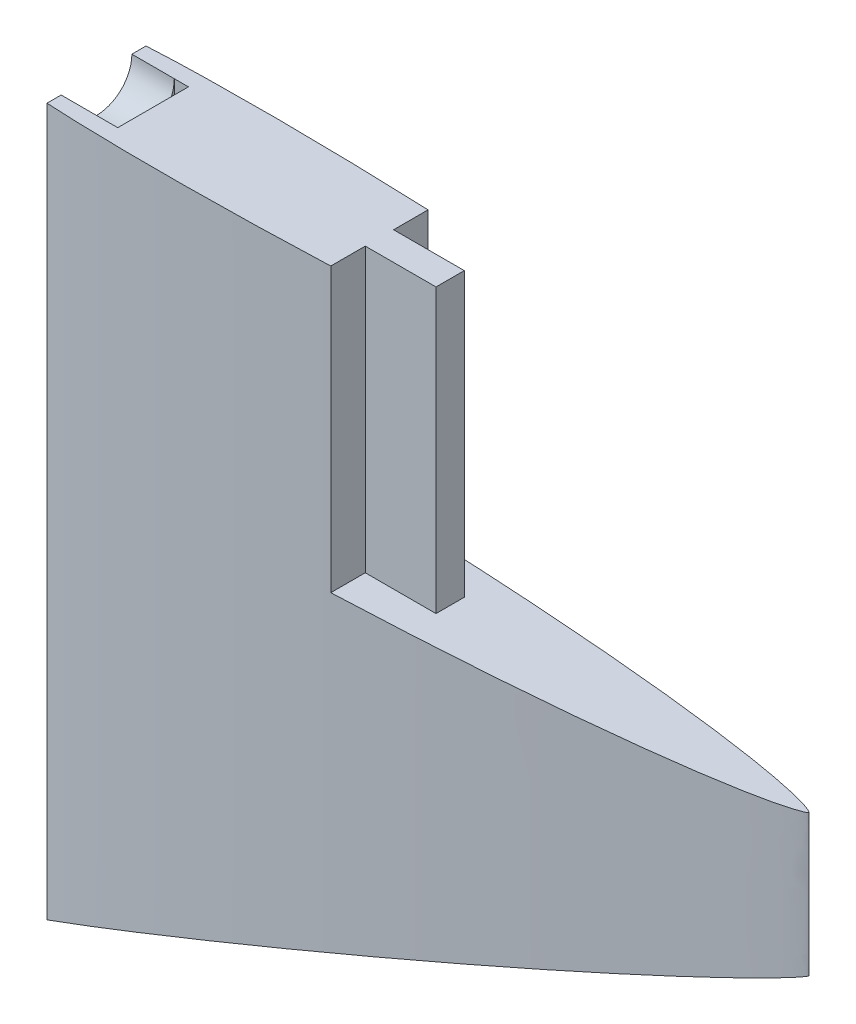
SolidWorks part; units mm, degrees
ref_plane "前视基准面" through (0, 0, 0) normal (0, 0, 1) x (1, 0, 0)
ref_plane "上视基准面" through (0, 0, 0) normal (0, 1, 0) x (1, 0, 0)
ref_plane "右视基准面" through (0, 0, 0) normal (1, 0, 0) x (0, 0, -1)
other "Configuration Table"
sketch "草图1" plane through (0, 0, 0) normal (0, 1, 0) x (1, 0, 0)
  line L0 (-2000, 0) -> (98000, 0) construction
  line L1 (0, -2000) -> (0, 98000) construction
  line L2 (0, 3.5) -> (0, -3.5)
  spline S0 degree 4 poles (50.3662, 0) (50.3616, -0.0076) (50.3512, -0.0201) (50.3319, -0.0346) (50.3036, -0.0542) (50.2676, -0.0756) (50.2125, -0.105) (50.1197, -0.1486) (49.9578, -0.2148) (49.6652, -0.3175) (49.1393, -0.4735) (48.2702, -0.6887) (46.7082, -1.0116) (44.5066, -1.3804) (41.7789, -1.7599) (38.6521, -2.1248) (35.5143, -2.4387) (32.3724, -2.71) (29.2277, -2.9446) (26.0806, -3.1456) (22.9317, -3.3152) (19.7813, -3.4544) (16.6297, -3.5633) (13.4772, -3.6409) (10.324, -3.6857) (7.1705, -3.6936) (4.1946, -3.6609) (2.0077, -3.5999) (0.6097, -3.5385) (0, -3.5) knots 0 0 0 0 0 0.000699 0.001288 0.00188 0.002733 0.003996 0.006219 0.009974 0.016536 0.028475 0.049524 0.080651 0.142462 0.204716 0.26697 0.329223 0.391477 0.453731 0.515984 0.578238 0.640492 0.702745 0.764999 0.827253 0.889506 0.95176 1 1 1 1 1 construction
  spline S1 degree 4 poles (50.3662, 0) (50.3616, -0.0076) (50.3512, -0.0201) (50.3319, -0.0346) (50.3036, -0.0542) (50.2676, -0.0756) (50.2125, -0.105) (50.1197, -0.1486) (49.9578, -0.2148) (49.6652, -0.3175) (49.1393, -0.4735) (48.2702, -0.6887) (46.7082, -1.0116) (44.5066, -1.3804) (41.7789, -1.7599) (38.6521, -2.1248) (35.5143, -2.4387) (32.3724, -2.71) (29.2277, -2.9446) (26.0806, -3.1456) (22.9317, -3.3152) (19.7813, -3.4544) (16.6297, -3.5633) (13.4772, -3.6409) (10.324, -3.6857) (7.1705, -3.6936) (4.1946, -3.6609) (2.0077, -3.5999) (0.6097, -3.5385) (0, -3.5) knots 0 0 0 0 0 0.000699 0.001288 0.00188 0.002733 0.003996 0.006219 0.009974 0.016536 0.028475 0.049524 0.080651 0.142462 0.204716 0.26697 0.329223 0.391477 0.453731 0.515984 0.578238 0.640492 0.702745 0.764999 0.827253 0.889506 0.95176 1 1 1 1 1
  spline S2 degree 4 poles (50.3662, 0) (50.3616, 0.0076) (50.3512, 0.0201) (50.3319, 0.0346) (50.3036, 0.0542) (50.2676, 0.0756) (50.2125, 0.105) (50.1197, 0.1486) (49.9578, 0.2148) (49.6652, 0.3175) (49.1393, 0.4735) (48.2702, 0.6887) (46.7082, 1.0116) (44.5066, 1.3804) (41.7789, 1.7599) (38.6521, 2.1248) (35.5143, 2.4387) (32.3724, 2.71) (29.2277, 2.9446) (26.0806, 3.1456) (22.9317, 3.3152) (19.7813, 3.4544) (16.6297, 3.5633) (13.4772, 3.6409) (10.324, 3.6857) (7.1705, 3.6936) (4.1946, 3.6609) (2.0077, 3.5999) (0.6097, 3.5385) (0, 3.5) knots 0 0 0 0 0 0.000699 0.001288 0.00188 0.002733 0.003996 0.006219 0.009974 0.016536 0.028475 0.049524 0.080651 0.142462 0.204716 0.26697 0.329223 0.391477 0.453731 0.515984 0.578238 0.640492 0.702745 0.764999 0.827253 0.889506 0.95176 1 1 1 1 1
  point P8 (0, 0)
  dimension "D1" = 7
extrude "凸台-拉伸2" add sketch "草图1" along normal blind 100
sketch "草图3" plane through (0, 0, 0) normal (0, 0, 1) x (1, 0, 0)
  line L0 (50.3662, 100) -> (50.3662, 80)
  line L1 (50.3662, 80) -> (0, 100)
  line L2 (0, 100) -> (50.3662, 100)
  line L3 (-1000, 50) -> (49000, 50) construction
  line L4 (0, 0) -> (50.3662, 0)
  line L5 (50.3662, 0) -> (50.3662, 100)
  line L6 (50.3662, 100) -> (0, 100)
  line L7 (0, 100) -> (0, 0)
  line L8 (0, 0) -> (50.3662, 0) construction
  line L9 (50.3662, 0) -> (50.3662, 100) construction
  line L10 (50.3662, 100) -> (0, 100) construction
  line L11 (0, 100) -> (0, 0) construction
  line L12 (50.3662, 0) -> (50.3662, 20)
  line L13 (0, 0) -> (50.3662, 0)
  line L14 (50.3662, 20) -> (0, 0)
  point P8 (0, 50)
  dimension "D2" = 20
  dimension "D1" = 0
extrude "切除-拉伸1" cut sketch "草图3" against normal blind 100 and the other way blind 100
sketch "草图6" plane through (0, 0, 0) normal (0, 0, 1) x (1, 0, 0)
  line L0 (-1000, 50) -> (49000, 50) construction
  line L1 (0, 50) -> (20, 50)
  line L2 (20, 50) -> (20, 30)
  line L3 (20, 30) -> (50.3662, 30)
  line L4 (0, 0) -> (50.3662, 20)
  line L5 (50.3662, 20) -> (50.3662, 80)
  line L6 (50.3662, 80) -> (0, 100)
  line L7 (0, 100) -> (0, 0)
  line L8 (0, 0) -> (50.3662, 20) construction
  line L9 (50.3662, 20) -> (50.3662, 80) construction
  line L10 (50.3662, 80) -> (0, 100) construction
  line L11 (0, 100) -> (0, 0) construction
  line L12 (50.3662, 30) -> (50.3662, 20)
  line L13 (50.3662, 20) -> (0, 0)
  line L14 (0, 0) -> (0, 50)
  point P7 (0, 50)
  dimension "D2" = 20
  dimension "D3" = 20
  dimension "D1" = 0
sketch "草图7" plane through (0, 0, 0) normal (0, 0, 1) x (1, 0, 0)
  line L0 (0, 50) -> (20, 50) construction
  line L1 (0, 50) -> (20, 50)
  line L2 (20, 30) -> (50.3662, 30) construction
  line L3 (20, 50) -> (20, 30) construction
  line L4 (20, 30) -> (50.3662, 30)
  line L5 (20, 50) -> (20, 30)
  line L6 (0, 50) -> (0, 100)
  line L7 (0, 100) -> (50.3662, 80)
  line L8 (50.3662, 80) -> (50.3662, 30)
extrude "切除-拉伸2" cut sketch "草图7" against normal blind 10 and the other way blind 10
sketch "草图8" plane through (0, 0, 0) normal (1, 0, 0) x (0, 0, -1)
  line L0 (-3.5, 50) -> (3.5, 50) construction
  circle A0 centre (0, 50) radius 2.5
  dimension "D1" = 5
extrude "切除-拉伸3" cut sketch "草图8" along normal blind 4
sketch "草图9" plane through (0, 0, 0) normal (0, 1, 0) x (1, 0, 0)
  line L0 (4, 2.5) -> (3, 2.5)
  line L1 (3, 2.5) -> (3, -2.5)
  line L2 (3, -2.5) -> (4, -2.5)
  line L3 (4, -2.5) -> (4, 2.5)
  line L4 (0, 2.5) -> (0, -2.5)
  line L5 (0, -2.5) -> (4, -2.5)
  line L6 (4, -2.5) -> (4, 2.5)
  line L7 (4, 2.5) -> (0, 2.5)
  line L8 (0, 2.5) -> (0, -2.5) construction
  line L9 (0, -2.5) -> (4, -2.5) construction
  line L10 (4, -2.5) -> (4, 2.5) construction
  line L11 (4, 2.5) -> (0, 2.5) construction
  dimension "D2" = 1
  dimension "D1" = 0
extrude "切除-拉伸4" cut sketch "草图9" along normal blind 20 from offset 30 contours L3 L0 L1 L2
sketch "草图11" plane through (0, 0, 0) normal (0, 1, 0) x (1, 0, 0)
  line L0 (20, -3.4394) -> (20, 3.4394) construction
  line L1 (20, -3.4394) -> (20, 3.4394) construction
  line L2 (20, 1) -> (20, -1)
  line L3 (20, 1) -> (25, 1)
  line L4 (25, 1) -> (25, -1)
  line L5 (25, -1) -> (20, -1)
  point P5 (20, 0)
  dimension "D1" = 2
  dimension "D2" = 5
extrude "凸台-拉伸4" add sketch "草图11" along normal blind 20 from offset 30
